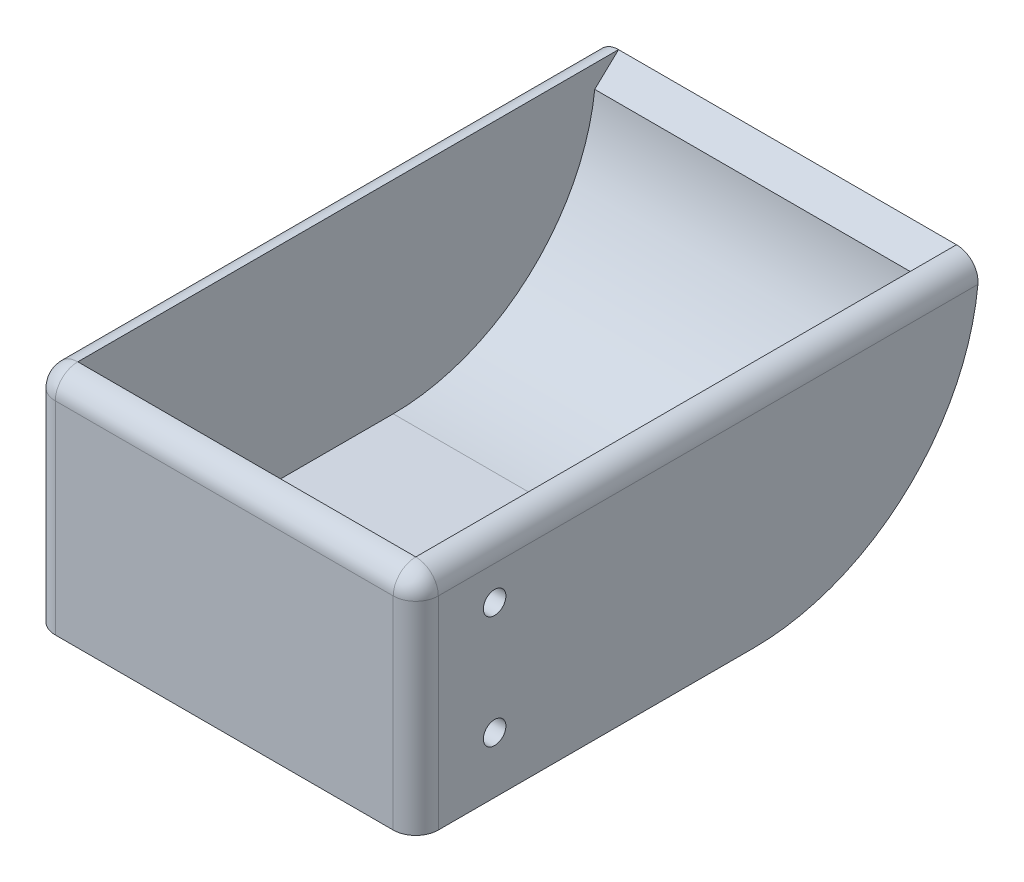
SolidWorks part; units mm, degrees
ref_plane "Front Plane" through (0, 0, 0) normal (0, 0, 1) x (1, 0, 0)
ref_plane "Top Plane" through (0, 0, 0) normal (0, 1, 0) x (1, 0, 0)
ref_plane "Right Plane" through (0, 0, 0) normal (1, 0, 0) x (0, 0, -1)
sketch "Sketch1" plane through (0, 0, 0) normal (1, 0, 0) x (0, 0, -1)
  line L0 (-60.96, 0) -> (-63.5, 0)
  line L1 (-63.5, 0) -> (-63.5, -25.4)
  line L2 (-63.5, -25.4) -> (-25.4, -25.4)
  line L3 (-60.96, 0) -> (-60.96, -22.86)
  line L5 (-60.96, -22.86) -> (-25.4, -22.86)
  line L6 (-2.6815, -2.54) -> (0, 0)
  line L8 (0, 0) -> (-63.5, 0) construction
  line L9 (-2.6815, -2.54) -> (-60.96, -2.54) construction
  line L10 (-60.96, -2.54) -> (-60.96, -22.86) construction
  arc A0 (-25.4, -25.4) -> (0, 0) centre (-25.4, 0) ccw
  arc A1 (-25.4, -22.86) -> (-2.6815, -2.54) centre (-25.4, 0) ccw
  dimension "D1" = 63.5
  dimension "D2" = 25.4
  dimension "D3" = 2.54
extrude "Boss-Extrude2" add sketch "Sketch1" along normal blind 38.1
sketch "Sketch2" plane through (38.1, 0, 0) normal (1, 0, 0) x (0, 0, -1)
  line L0 (-63.5, 0) -> (0, 0)
  line L1 (-63.5, 0) -> (-63.5, -25.4)
  line L2 (-63.5, -25.4) -> (-25.4, -25.4)
  arc A0 (-25.4, -25.4) -> (0, 0) centre (-25.4, 0) ccw
extrude "Boss-Extrude3" add sketch "Sketch2" along normal blind 2.54
sketch "Sketch3" plane through (0, 0, 0) normal (-1, 0, 0) x (0, 0, 1)
  line L0 (0, 0) -> (63.5, 0)
  line L1 (63.5, 0) -> (63.5, -25.4)
  line L2 (63.5, 0) -> (63.5, -25.4) construction
  line L3 (63.5, -25.4) -> (25.4, -25.4)
  arc A0 (25.4, -25.4) -> (0, 0) centre (25.4, 0) cw
  arc M1 (0, 0) -> (25.4, -25.4) centre (25.4, 0) ccw
  line M2 (25.4, -25.4) -> (63.5, -25.4)
  line M3 (63.5, -25.4) -> (63.5, 0)
  line M4 (63.5, 0) -> (60.96, 0)
  line M5 (60.96, 0) -> (60.96, -22.86)
  line M6 (60.96, -22.86) -> (25.4, -22.86)
  arc M7 (25.4, -22.86) -> (2.6815, -2.54) centre (25.4, 0) cw
  line M8 (2.6815, -2.54) -> (0, 0)
extrude "Boss-Extrude5" add sketch "Sketch3" along normal blind 2.54 contours M8 M1 M2 M3 M4 M5 M6 M7 | L0 M8 M7 M6 M5 region at (0, -1.7665, 0.8705) region at (0, -10.8244, 33.8765)
fillet "Fillet1" radius 2.54 1 edges at (40.64, 0, 31.75)
fillet "Fillet3" radius 2.54 1 edges at (-2.54, 0, 31.75)
fillet "Fillet5" radius 2.54 5 edges at (40.64, -13.97, 63.5) (39.8961, -0.7439, 63.5) (-2.54, -13.97, 63.5) (-1.7961, -0.7439, 63.5) (19.05, 0, 63.5)
ref_plane "Plane1" through (40.64, 0, 0) normal (1, 0, 0) x (0, 0, -1)
sketch "Sketch5" plane through (40.64, 0, 0) normal (1, 0, 0) x (0, 0, -1)
  line L0 (-60.96, -25.4) -> (-25.4, -25.4) construction
  line L2 (0, 0) -> (-60.96, 0) construction
  line L3 (-60.96, -2.54) -> (-60.96, -25.4) construction
  circle A0 centre (-54.61, -6.35) radius 1.27
  circle A1 centre (-54.61, -19.05) radius 1.27
  dimension "D5" = 2.54
  dimension "D6" = 2.54
  dimension "D1" = 6.35
  dimension "D2" = 6.35
  dimension "D3" = 6.35
  dimension "D4" = 6.35
extrude "Cut-Extrude1" cut sketch "Sketch5" against normal blind 2.54
